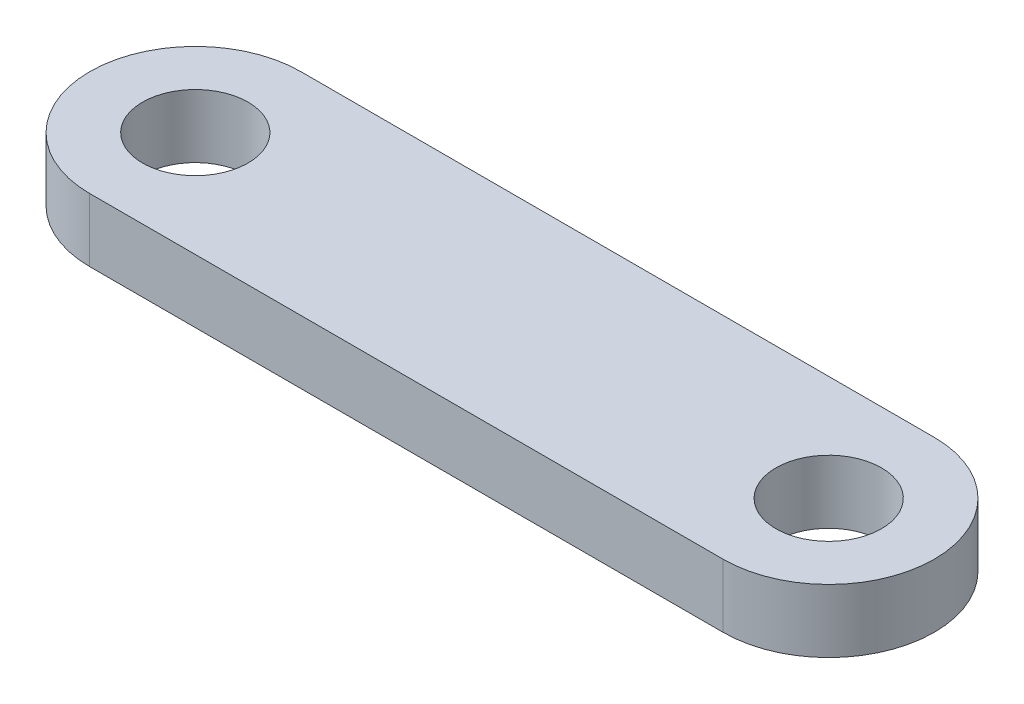
SolidWorks part; units mm, degrees
ref_plane "Front Plane" through (0, 0, 0) normal (0, 0, 1) x (1, 0, 0)
ref_plane "Top Plane" through (0, 0, 0) normal (0, 1, 0) x (1, 0, 0)
ref_plane "Right Plane" through (0, 0, 0) normal (1, 0, 0) x (0, 0, -1)
sketch "Sketch1" plane through (0, 0, 0) normal (0, 1, 0) x (1, 0, 0)
  line L0 (-19.05, 0) -> (19.05, 0) construction
  line L1 (-19.05, 6.35) -> (19.05, 6.35)
  line L2 (-19.05, -6.35) -> (19.05, -6.35)
  arc A0 (-19.05, 6.35) -> (-19.05, -6.35) centre (-19.05, 0) ccw
  arc A1 (19.05, -6.35) -> (19.05, 6.35) centre (19.05, 0) ccw
  circle A2 centre (-19.05, 0) radius 3.175
  circle A3 centre (19.05, 0) radius 3.175
  point P3 (0, 0)
  dimension "D2" = 6.35
  dimension "D3" = 6.35
  dimension "D4" = 6.35
  dimension "D1" = 38.1
extrude "Boss-Extrude1" add sketch "Sketch1" along normal blind 3.81
